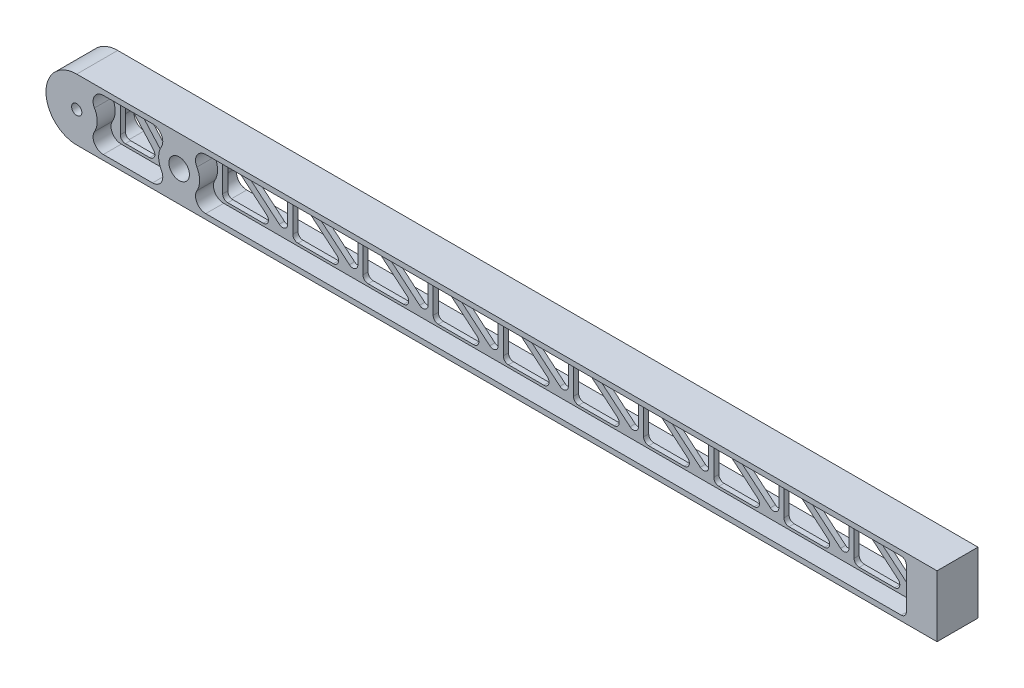
SolidWorks part; units mm, degrees
material "6061-T6 (SS)"
ref_plane "Front Plane" through (0, 0, 0) normal (0, 0, 1) x (1, 0, 0)
ref_plane "Top Plane" through (0, 0, 0) normal (0, 1, 0) x (1, 0, 0)
ref_plane "Right Plane" through (0, 0, 0) normal (1, 0, 0) x (0, 0, -1)
sketch "Sketch1" plane through (0, 0, 0) normal (0, 0, 1) x (1, 0, 0)
  line L0 (0, 0) -> (63.5, 0) construction
  line L3 (533.4, 19.05) -> (533.4, -19.05)
  line L73 (4.3277, -1.5448) -> (2.1108, 2.3718) construction
  line L82 (4.3277, -1.5448) -> (2.1108, 2.3718) construction
  line L201 (0, 19.05) -> (533.4, 19.05)
  line L204 (4.3277, -1.5448) -> (2.1108, 2.3718) construction
  line L205 (4.3277, -1.5448) -> (2.1108, 2.3718) construction
  line L206 (4.3277, -1.5448) -> (2.1108, 2.3718) construction
  line L210 (0, -19.05) -> (533.4, -19.05)
  circle A0 centre (0, 0) radius 3.175
  circle A1 centre (63.5, 0) radius 12.7
  circle A2 centre (63.5, 0) radius 6.35
  circle A3 centre (0, 0) radius 19.05
  dimension "D5" = 25.4
  dimension "D6" = 38.1
  dimension "D7" = 6.35
  dimension "D8" = 12.7
  dimension "D1" = 63.5
  dimension "D2" = 533.4
  dimension "D3" = 38.1
extrude "Boss-Extrude1" add sketch "Sketch1" along normal mid plane 25.4 contours A3 A0 | A3 | A3 | A0 | A3 L210 A1 | A3 A1 | A3 A1 | A3 A1 | A2 | A1 A2 | A1 | A1 | A1 | A1 L201 | A1 L210 | L210 L3 | L3 | L3 L201 region at (279.7099, 0, 0) region at (13.0894, 13.0894, 0) region at (0, 0, 0) region at (51.1592, 0, 0) region at (63.5, 0, 0)
extrude "Cut-Extrude3" cut sketch "Sketch1<10>" against normal mid plane 25.4 contours A0 | A2
sketch "Sketch1<10>" plane through (0, 0, 0) normal (0, 0, 1) x (1, 0, 0) same geometry as "Sketch1"
sketch "Sketch3" plane through (0, 0, 12.7) normal (0, 0, 1) x (1, 0, 0)
  line L0 (63.5, 0) -> (63.5, -15.875) construction
  line L1 (16.4978, -15.875) -> (47.0022, -15.875)
  line L2 (76.2, 14.6141) -> (76.2, 15.875)
  line L3 (16.4978, 15.875) -> (47.0022, 15.875)
  line L5 (76.2, -15.875) -> (514.35, -15.875)
  line L6 (76.2, -15.875) -> (76.2, -14.6141)
  line L7 (76.2, 15.875) -> (514.35, 15.875)
  line L8 (514.35, -15.875) -> (514.35, 15.875)
  line L9 (0, -19.05) -> (533.4, -19.05) construction
  line L10 (533.4, 19.05) -> (533.4, -19.05) construction
  line L11 (15.875, 14.2875) -> (15.875, -14.2875)
  line L12 (15.875, -14.2875) -> (41.2295, -14.2875)
  line L13 (41.2295, -14.2875) -> (15.875, 14.2875)
  line L14 (22.2705, 14.2875) -> (47.625, -14.2875)
  line L15 (47.625, -14.2875) -> (47.625, 14.2875)
  line L16 (47.625, 14.2875) -> (22.2705, 14.2875)
  line L17 (28.5523, 0) -> (32.1306, 3.175)
  line L18 (79.375, 14.2875) -> (79.375, -14.2875)
  line L19 (79.375, -14.2875) -> (113.2552, -14.2875)
  line L20 (113.2552, -14.2875) -> (79.375, 14.2875)
  line L21 (85.8173, 14.2875) -> (119.6975, -14.2875)
  line L22 (119.6975, -14.2875) -> (119.6975, 14.2875)
  line L23 (119.6975, 14.2875) -> (85.8173, 14.2875)
  line L24 (98.9929, 3.175) -> (96.3151, 0)
  line L25 (122.8725, 14.2875) -> (122.8725, -14.2875)
  line L26 (122.8725, -14.2875) -> (156.7527, -14.2875)
  line L27 (156.7527, -14.2875) -> (122.8725, 14.2875)
  line L28 (129.3148, 14.2875) -> (163.195, -14.2875)
  line L29 (163.195, -14.2875) -> (163.195, 14.2875)
  line L30 (163.195, 14.2875) -> (129.3148, 14.2875)
  line L31 (142.4904, 3.175) -> (139.8126, 0)
  line L32 (166.37, 14.2875) -> (166.37, -14.2875)
  line L33 (166.37, -14.2875) -> (200.2502, -14.2875)
  line L34 (200.2502, -14.2875) -> (166.37, 14.2875)
  line L35 (172.8123, 14.2875) -> (206.6925, -14.2875)
  line L36 (206.6925, -14.2875) -> (206.6925, 14.2875)
  line L37 (206.6925, 14.2875) -> (172.8123, 14.2875)
  line L38 (185.9879, 3.175) -> (183.3101, 0)
  line L39 (209.8675, 14.2875) -> (209.8675, -14.2875)
  line L40 (209.8675, -14.2875) -> (243.7477, -14.2875)
  line L41 (243.7477, -14.2875) -> (209.8675, 14.2875)
  line L42 (216.3098, 14.2875) -> (250.19, -14.2875)
  line L43 (250.19, -14.2875) -> (250.19, 14.2875)
  line L44 (250.19, 14.2875) -> (216.3098, 14.2875)
  line L45 (229.4854, 3.175) -> (226.8076, 0)
  line L46 (253.365, 14.2875) -> (253.365, -14.2875)
  line L47 (253.365, -14.2875) -> (287.2452, -14.2875)
  line L48 (287.2452, -14.2875) -> (253.365, 14.2875)
  line L49 (259.8073, 14.2875) -> (293.6875, -14.2875)
  line L50 (293.6875, -14.2875) -> (293.6875, 14.2875)
  line L51 (293.6875, 14.2875) -> (259.8073, 14.2875)
  line L52 (272.9829, 3.175) -> (270.3051, 0)
  line L53 (296.8625, 14.2875) -> (296.8625, -14.2875)
  line L54 (296.8625, -14.2875) -> (330.7427, -14.2875)
  line L55 (330.7427, -14.2875) -> (296.8625, 14.2875)
  line L56 (303.3048, 14.2875) -> (337.185, -14.2875)
  line L57 (337.185, -14.2875) -> (337.185, 14.2875)
  line L58 (337.185, 14.2875) -> (303.3048, 14.2875)
  line L59 (316.4804, 3.175) -> (313.8026, 0)
  line L60 (340.36, 14.2875) -> (340.36, -14.2875)
  line L61 (340.36, -14.2875) -> (374.2402, -14.2875)
  line L62 (374.2402, -14.2875) -> (340.36, 14.2875)
  line L63 (346.8023, 14.2875) -> (380.6825, -14.2875)
  line L64 (380.6825, -14.2875) -> (380.6825, 14.2875)
  line L65 (380.6825, 14.2875) -> (346.8023, 14.2875)
  line L66 (359.9779, 3.175) -> (357.3001, 0)
  line L67 (383.8575, 14.2875) -> (383.8575, -14.2875)
  line L68 (383.8575, -14.2875) -> (417.7377, -14.2875)
  line L69 (417.7377, -14.2875) -> (383.8575, 14.2875)
  line L70 (390.2998, 14.2875) -> (424.18, -14.2875)
  line L71 (424.18, -14.2875) -> (424.18, 14.2875)
  line L72 (424.18, 14.2875) -> (390.2998, 14.2875)
  line L73 (403.4754, 3.175) -> (400.7976, 0)
  line L74 (427.355, 14.2875) -> (427.355, -14.2875)
  line L75 (427.355, -14.2875) -> (461.2352, -14.2875)
  line L76 (461.2352, -14.2875) -> (427.355, 14.2875)
  line L77 (433.7973, 14.2875) -> (467.6775, -14.2875)
  line L78 (467.6775, -14.2875) -> (467.6775, 14.2875)
  line L79 (467.6775, 14.2875) -> (433.7973, 14.2875)
  line L80 (446.9729, 3.175) -> (444.2951, 0)
  line L81 (470.8525, 14.2875) -> (470.8525, -14.2875)
  line L82 (470.8525, -14.2875) -> (504.7327, -14.2875)
  line L83 (504.7327, -14.2875) -> (470.8525, 14.2875)
  line L84 (477.2948, 14.2875) -> (511.175, -14.2875)
  line L85 (511.175, -14.2875) -> (511.175, 14.2875)
  line L86 (511.175, 14.2875) -> (477.2948, 14.2875)
  line L87 (490.4704, 3.175) -> (487.7926, 0)
  line L88 (50.8, 15.875) -> (76.2, 15.875)
  line L89 (50.8, -15.875) -> (76.2, -15.875)
  line L93 (0, 19.05) -> (533.4, 19.05) construction
  arc A0 (52.5015, 6.35) -> (47.0022, 15.875) centre (47.0022, 9.525) ccw
  arc A1 (52.5015, 6.35) -> (52.5015, -6.35) centre (63.5, 0) ccw
  arc A2 (10.9985, 6.35) -> (16.4978, 15.875) centre (16.4978, 9.525) cw
  arc A3 (10.9985, -6.35) -> (16.4978, -15.875) centre (16.4978, -9.525) ccw
  arc A4 (10.9985, -6.35) -> (10.9985, 6.35) centre (0, 0) ccw
  arc A5 (52.5015, -6.35) -> (47.0022, -15.875) centre (47.0022, -9.525) cw
  arc A6 (74.4985, -6.35) -> (79.9978, -15.875) centre (79.9978, -9.525) ccw
  arc A7 (74.4985, 6.35) -> (79.9978, 15.875) centre (79.9978, 9.525) cw
  arc A8 (74.4985, -6.35) -> (74.4985, 6.35) centre (63.5, 0) ccw
  point P18 (533.4, 0)
  dimension "D3" = 12.7
  dimension "D4" = 25.4
  dimension "D7" = 15.875
  dimension "D10" = 6.35
  dimension "D2" = 3.175
  dimension "D5" = 19.05
  dimension "D6" = 3.175
  dimension "D8" = 1.5875
  dimension "D9" = 1.5875
  dimension "D11" = 15.875
  dimension "D12" = 3.175
  dimension "D13" = 1.5875
  dimension "D14" = 1.5875
  dimension "D15" = 3.175
  dimension "D16" = 3.175
  dimension "D18" = 1.5875
  dimension "D19" = 10
  dimension "D20" = 3.175
  dimension "D17" = 1.5875
  dimension "D21" = 3.175
  dimension "D22" = 3.175
extrude "Cut-Extrude5" cut sketch "Sketch3" against normal through all contours L12 L13 L11 | L15 L16 L14 | L19 L20 L18 | L22 L23 L21 | L26 L27 L25 | L29 L30 L28 | L40 L41 L39 | L47 L48 L46 | L50 L51 L49 | L54 L55 L53 | L57 L58 L56 | L61 L62 L60 | L64 L65 L63 | L68 L69 L67 | L71 L72 L70 | L75 L76 L74 | L78 L79 L77 | L82 L83 L81 | L85 L86 L84 | L34 L32 L33 | L37 L35 L36 | L44 L42 L43 region at (24.3265, -4.7625, 12.7) region at (39.1735, 4.7625, 12.7) region at (90.6684, -4.7625, 12.7) region at (108.4041, 4.7625, 12.7) region at (134.1659, -4.7625, 12.7) region at (151.9016, 4.7625, 12.7) region at (221.1609, -4.7625, 12.7) region at (264.6584, -4.7625, 12.7) region at (282.3941, 4.7625, 12.7) region at (308.1559, -4.7625, 12.7) region at (325.8916, 4.7625, 12.7) region at (351.6534, -4.7625, 12.7) region at (369.3891, 4.7625, 12.7) region at (395.1509, -4.7625, 12.7) region at (412.8866, 4.7625, 12.7) region at (438.6484, -4.7625, 12.7) region at (456.3841, 4.7625, 12.7) region at (482.1459, -4.7625, 12.7) region at (499.8816, 4.7625, 12.7)
extrude "Cut-Extrude7" cut sketch "Sketch3<5>" against normal blind 11.1125 contours A5 A1 A0 L3 A2 A4 A3 L1 L13 L12 L11 L14 L16 L15 | A8 A6 L5 L8 L7 A7 L86 L85 L84 L83 L82 L81 L79 L78 L77 L76 L75 L74 L72 L71 L70 L69 L68 L67 L65 L64 L63 L62 L61 L60 region at (31.75, 0, 12.7) region at (78.1362, 15.1322, 12.7)
sketch "Sketch3<5>" plane through (0, 0, 12.7) normal (0, 0, 1) x (1, 0, 0) same geometry as "Sketch3"
mirror "Mirror1" about plane through (0, 0, 0) normal (0, 0, 1) of "Cut-Extrude7"
fillet "Fillet1" radius 3.175 68 edges at (119.6975, 14.2875, 0) (119.6975, -14.2875, 0) (85.8173, 14.2875, 0) (163.195, 14.2875, 0) (163.195, -14.2875, 0) (129.3148, 14.2875, 0) (206.6925, 14.2875, 0) (206.6925, -14.2875, 0) (172.8123, 14.2875, 0) (250.19, 14.2875, 0) (250.19, -14.2875, 0) (216.3098, 14.2875, 0) (293.6875, 14.2875, 0) (293.6875, -14.2875, 0) (259.8073, 14.2875, 0) (337.185, 14.2875, 0) (337.185, -14.2875, 0) (303.3048, 14.2875, 0) (380.6825, 14.2875, 0) (380.6825, -14.2875, 0) (346.8023, 14.2875, 0) (424.18, 14.2875, 0) (424.18, -14.2875, 0) (390.2998, 14.2875, 0) (467.6775, 14.2875, 0) (467.6775, -14.2875, 0) (433.7973, 14.2875, 0) (511.175, 14.2875, 0) (511.175, -14.2875, 0) (477.2948, 14.2875, 0) (79.375, 14.2875, 0) (113.2552, -14.2875, 0) (122.8725, 14.2875, 0) (156.7527, -14.2875, 0) (122.8725, -14.2875, 0) (166.37, 14.2875, 0) (200.2502, -14.2875, 0) (166.37, -14.2875, 0) (209.8675, 14.2875, 0) (243.7477, -14.2875, 0) (209.8675, -14.2875, 0) (253.365, 14.2875, 0) (287.2452, -14.2875, 0) (253.365, -14.2875, 0) (296.8625, 14.2875, 0) (330.7427, -14.2875, 0) (296.8625, -14.2875, 0) (340.36, 14.2875, 0) (374.2402, -14.2875, 0) (340.36, -14.2875, 0) (383.8575, 14.2875, 0) (417.7377, -14.2875, 0) (383.8575, -14.2875, 0) (427.355, 14.2875, 0) (461.2352, -14.2875, 0) (427.355, -14.2875, 0) (470.8525, 14.2875, 0) (504.7327, -14.2875, 0) (470.8525, -14.2875, 0) (79.375, -14.2875, 0) (22.2705, 14.2875, 0) (47.625, 14.2875, 0) (47.625, -14.2875, 0) (41.2295, -14.2875, 0) (15.875, 14.2875, 0) (15.875, -14.2875, 0) (514.35, -15.875, 7.1437) (514.35, 15.875, 7.1437)
